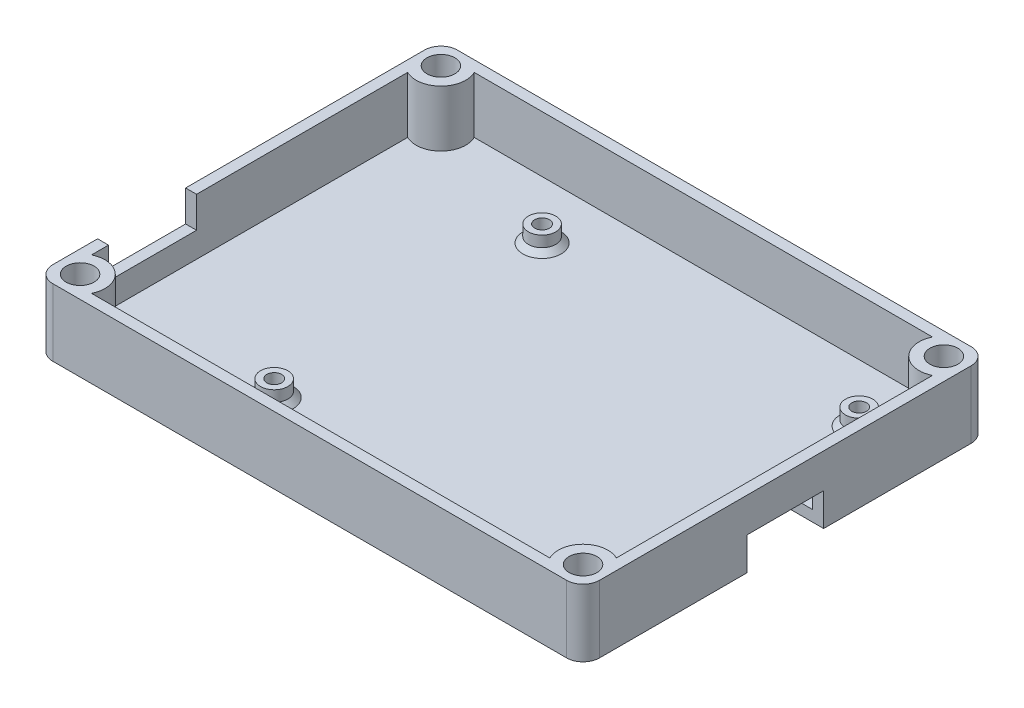
SolidWorks part; units mm, degrees
ref_plane "Front Plane" through (0, 0, 0) normal (0, 0, 1) x (1, 0, 0)
ref_plane "Top Plane" through (0, 0, 0) normal (0, 1, 0) x (1, 0, 0)
ref_plane "Right Plane" through (0, 0, 0) normal (1, 0, 0) x (0, 0, -1)
sketch "Sketch1" plane through (0, 0, 0) normal (0, 1, 0) x (1, 0, 0)
  line L1 (-50, -37) -> (50, -37)
  line L2 (-50, -37) -> (-50, 37)
  line L3 (-50, 37) -> (50, 37)
  line L4 (50, -37) -> (50, 37)
  line L5 (-50, -37) -> (50, 37) construction
  line L6 (-50, 37) -> (50, -37) construction
  circle A0 centre (46, -33) radius 2.5527
  circle A1 centre (-46, -33) radius 2.5527
  circle A2 centre (-46, 33) radius 2.5527
  circle A3 centre (46, 33) radius 2.5527
  point P0 (0, 0)
  dimension "D3" = 5.1054
  dimension "D6" = 5.1054
  dimension "D9" = 5.1054
  dimension "D12" = 5.1054
  dimension "D1" = 100
  dimension "D2" = 74
  dimension "D4" = 4
  dimension "D5" = 4
  dimension "D7" = 4
  dimension "D8" = 4
  dimension "D10" = 4
  dimension "D11" = 4
  dimension "D13" = 4
  dimension "D14" = 4
extrude "Boss-Extrude1" add sketch "Sketch1" along normal blind 12.3
shell "Shell1" thickness 2 removed face at (0, 12.3, 0)
sketch "Sketch2" plane through (0, 2, 0) normal (0, 1, 0) x (1, 0, 0)
  circle A0 centre (39, -24.5) radius 1.35 construction
  circle A1 centre (-19, -24.5) radius 1.35 construction
  circle A2 centre (-19, 24.5) radius 1.35 construction
  circle A3 centre (39, 24.5) radius 1.35 construction
  circle A4 centre (39, -24.5) radius 1.35
  circle A5 centre (-19, -24.5) radius 1.35
  circle A6 centre (-19, 24.5) radius 1.35
  circle A7 centre (39, 24.5) radius 1.35
  circle A8 centre (-19, 24.5) radius 2.5
  circle A9 centre (39, 24.5) radius 2.5
  circle A10 centre (-19, -24.5) radius 2.5
  circle A11 centre (39, -24.5) radius 2.5
  dimension "D1" = 5
  dimension "D2" = 5
  dimension "D3" = 5
  dimension "D4" = 5
extrude "Boss-Extrude2" add sketch "Sketch2" along normal blind 3
hole_wizard "CSK for M2.5 Countersunk Flat Head Screw1" positions "Sketch9" profile "Sketch10" countersink size "M2.5" standard "ISO" end condition through all
sketch "Sketch9" plane through (0, 0, 0) normal (0, -1, 0) x (-1, 0, 0)
  point P0 (19, -24.5)
  point P3 (19, 24.5)
  point P6 (-39, 24.5)
  point P9 (-39, -24.5)
sketch "Sketch10" plane through (-19, 0, 24.5) normal (1, 0, 0) x (0, 0, -1)
  line L0 (0, 0) -> (0, 12.3)
  line L1 (0, 12.3) -> (1.35, 12.3)
  line L2 (1.35, 12.3) -> (1.35, 1.4)
  line L3 (1.35, 1.4) -> (2.75, 0)
  line L5 (2.75, 0) -> (0, 0)
  line L6 (-1.35, 1.4) -> (-2.75, 0) construction
  line L11 (0, -6.35) -> (0, 107.95) construction
  dimension "Thru Hole Dia." = 2.7
  dimension "Thru Hole Depth" = 12.3
  dimension "Near C'Sink Dia." = 5.5
  dimension "Near C'Sink Angle" = 90
sketch "Sketch11" plane through (-50, 0, 0) normal (-1, 0, 0) x (0, 0, 1)
  line L4 (9.7, 6.6) -> (25.8, 6.6)
  line L5 (25.8, 6.6) -> (25.8, 20.1)
  line L6 (25.8, 20.1) -> (9.7, 20.1)
  line L7 (9.7, 20.1) -> (9.7, 6.6)
  line L8 (9.7, 6.6) -> (25.8, 6.6)
  line L9 (25.8, 6.6) -> (25.8, 20.1)
  line L10 (25.8, 20.1) -> (9.7, 20.1)
  line L11 (9.7, 20.1) -> (9.7, 6.6)
  dimension "D1" = 0
extrude "Cut-Extrude1" cut sketch "Sketch11" against normal blind 3
fillet "Fillet1" radius 3 4 edges at (50, 6.15, 37) (-50, 6.15, 37) (-50, 6.15, -37) (50, 6.15, -37)
sketch "Sketch16" plane through (0, 0, 0) normal (0, -1, 0) x (1, 0, 0)
  line L0 (45.5, 7) -> (45.5, -7)
  line L1 (45.5, 7) -> (50, 7)
  line L2 (45.5, -7) -> (50, -7)
  line L3 (50, 7) -> (50, -7)
  line L4 (28.5, 7) -> (28.5, -7)
  line L5 (28.5, -7) -> (45.5, -7)
  line L6 (45.5, -7) -> (45.5, 7)
  line L7 (45.5, 7) -> (28.5, 7)
  line L8 (28.5, 7) -> (28.5, -7)
  line L9 (28.5, -7) -> (45.5, -7)
  line L10 (45.5, -7) -> (45.5, 7)
  line L11 (45.5, 7) -> (28.5, 7)
  line L12 (50, 34) -> (50, -34) construction
  line L14 (45.5, -7) -> (39.5, -7)
  line L15 (45.5, -7) -> (45.5, 7)
  line L16 (45.5, 7) -> (39.5, 7)
  line L17 (39.5, -7) -> (39.5, 7)
  line M15 (50, -34) -> (50, 34)
  dimension "D2" = 6
  dimension "D1" = 0
extrude "Cut-Extrude3" cut sketch "Sketch16" against normal blind 6 contours L0 L2 L1 M15 | L15 L14 L17 L16 region at (47.75, 0, 0)
chamfer "Chamfer1" distance 1 angle 45 4 edges at (39, 2, 22) (39, 2, -27) (-19, 2, -27) (-19, 2, 22)
